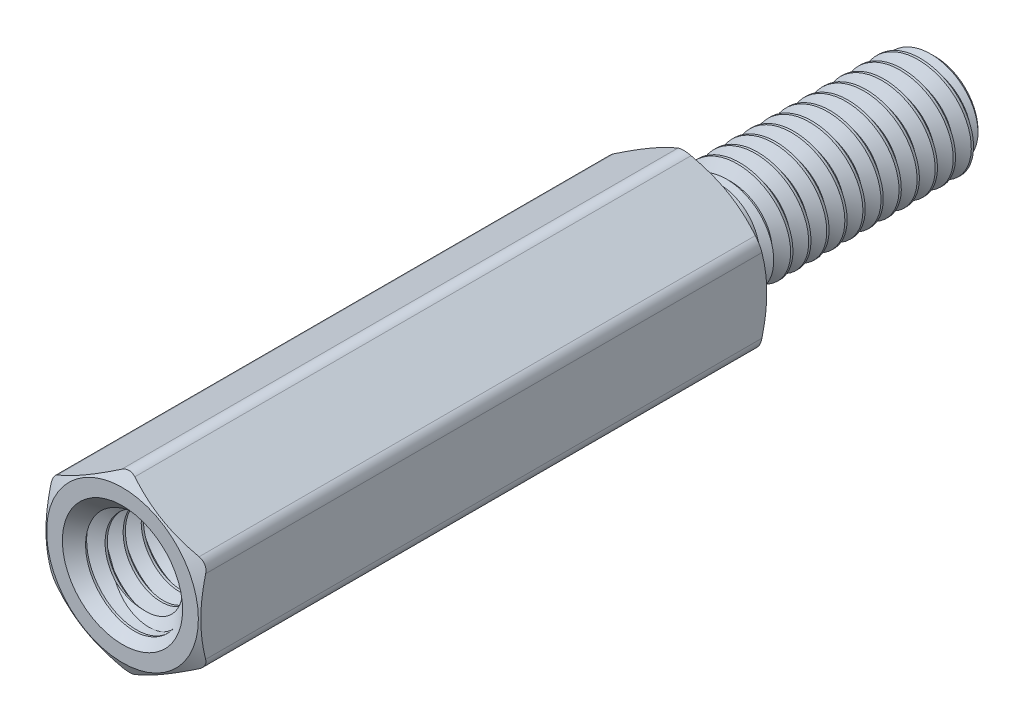
SolidWorks part; units mm, degrees
ref_plane "Front Plane" through (0, 0, 0) normal (0, 0, 1) x (1, 0, 0)
ref_plane "Top Plane" through (0, 0, 0) normal (0, 1, 0) x (1, 0, 0)
ref_plane "Right Plane" through (0, 0, 0) normal (1, 0, 0) x (0, 0, -1)
sketch "Sketch1" plane through (0, 0, 0) normal (0, 0, 1) x (1, 0, 0)
  line L1 (3, 1.7321) -> (0, 3.4641)
  line L2 (0, 3.4641) -> (-3, 1.7321)
  line L3 (-3, 1.7321) -> (-3, -1.7321)
  line L4 (-3, -1.7321) -> (0, -3.4641)
  line L5 (0, -3.4641) -> (3, -1.7321)
  line L6 (3, -1.7321) -> (3, 1.7321)
  circle A0 centre (0, 0) radius 3 construction
  point P10 (0, -3)
  dimension "Hex Size" = 6
sketch "Sketch2" plane through (0, 0, 0) normal (1, 0, 0) x (0, 0, -1)
  line L0 (9.5, 0) -> (-22, 0) construction
  line L2 (0, 2) -> (0, -2) construction
  line L3 (-10.9, 2) -> (-10.9, -2) construction
  line L4 (-22.6563, 2.0758) -> (-22.3063, 1.4696) construction
  line L5 (-22.3063, 1.4696) -> (-21.9563, 2.0758) construction
  line L6 (-21.9563, 2.0758) -> (-22.6563, 2.0758) construction
  line L7 (-22.6125, 2) -> (-22, 2) construction
  line L8 (-22.35, 1.5453) -> (-22.2625, 1.5453) construction
  line L9 (-22.3063, 1.5453) -> (-22.3063, 1.4696) construction
  line L10 (-22.3063, 2) -> (-22.3063, 2.0758) construction
  line L11 (9.4562, 2.0758) -> (10.1562, 2.0758) construction
  line L12 (10.1562, 2.0758) -> (9.8062, 1.4696) construction
  line L13 (9.8062, 1.4696) -> (9.4562, 2.0758) construction
  line L14 (9.5, 2) -> (10.1125, 2) construction
  line L15 (9.7625, 1.5453) -> (9.85, 1.5453) construction
  line L16 (9.8062, 1.5453) -> (9.8062, 1.4696) construction
  line L17 (9.8062, 2) -> (9.8062, 2.0758) construction
  line L18 (0, 3.4641) -> (-22, 3.4641) construction
  point P6 (0, 0)
  point P9 (-10.9, 0)
  dimension "Length" = 22
sketch "Sketch3" plane through (0, 0, 0) normal (1, 0, 0) x (0, 0, -1)
  line L0 (-10.9, 0) -> (9.5, 0)
  line L1 (-10.9, 2) -> (-10.9, -2) construction
  line L2 (9.5, 0) -> (9.5, 1.65)
  line L3 (9.5, 1.65) -> (9.15, 2)
  line L4 (9.15, 2) -> (1.4025, 2)
  line L5 (1.4025, 2) -> (1.14, 1.5453)
  line L6 (-10.9, 0) -> (-10.9, 1.65)
  line L7 (-10.9, 1.65) -> (-11.25, 2)
  line L8 (-11.25, 2) -> (-21.65, 2)
  line L9 (-21.65, 2) -> (-22, 2.35)
  line L10 (9.15, 0) -> (9.15, -2) construction
  line L11 (-22, 2.35) -> (-22, 3)
  line L12 (-22, 3) -> (0, 3)
  line L14 (1.14, 1.5453) -> (0.35, 1.5453)
  line L15 (0, 1.8953) -> (0, 3)
  arc A0 (0, 1.8953) -> (0.35, 1.5453) centre (0.35, 1.8953) ccw
  point P5 (-22, -3)
  point P8 (-20.25, -2)
  point P9 (7.75, -2)
  point P27 (0, 1.5453)
  dimension "D4" = 0.35
  dimension "D2" = 0.35
  dimension "D1" = 45
  dimension "D6" = 1.75
  dimension "D7" = 60
  dimension "D3" = 1.75
  dimension "D5" = 1.14
revolve "Revolve1" add sketch "Sketch3" angle 360 about L0
sketch "Sketch4" plane through (0, 0, 22) normal (0, 0, 1) x (1, 0, 0)
  line L0 (0, 3) -> (0, 2) construction
  line L1 (-3, 1.7321) -> (-3, -1.7321)
  line L2 (-3, -1.7321) -> (0, -3.4641)
  line L3 (0, -3.4641) -> (3, -1.7321)
  line L4 (3, -1.7321) -> (3, 1.7321)
  line L5 (3, 1.7321) -> (0, 3.4641)
  line L6 (0, 3.4641) -> (-3, 1.7321)
  circle A0 centre (0, 0) radius 3 construction
  circle A1 centre (0, 0) radius 2.5
  circle A2 centre (0, 0) radius 3 construction
  point P16 (0, 2.5)
extrude "Boss-Extrude1" add sketch "Sketch4" against normal up to surface (22 mm away) up to face at (0, 3, 0)
sketch "Sketch5" plane through (0, 0, 22) normal (0, 0, 1) x (1, 0, 0)
  line L0 (-1.1472, 1.6383) -> (1.1472, -1.6383) construction
  line L1 (0, 2) -> (0, -2) construction
  line L3 (0, -2.7928) -> (0, 2.7928) construction
  circle A0 centre (0, 0) radius 2.94
  point P11 (1.1472, -1.6383)
  dimension "D1" = 5.88
  dimension "D2" = 35
extrude "Cut-Extrude1" cut sketch "Sketch5" against normal through all draft 60 flip side to cut
sketch "Sketch6" plane through (0, 0, 0) normal (0, 0, -1) x (-1, 0, 0)
  circle A0 centre (0, 0) radius 2.94
  circle A1 centre (0, 0) radius 2.94 construction
extrude "Cut-Extrude2" cut sketch "Sketch6" against normal through all draft 60 flip side to cut
fillet "Fillet1" radius 0.51 6 edges at (0, 3.4641, 11) (-3, -1.7321, 11) (0, -3.4641, 11) (3, -1.7321, 11) (3, 1.7321, 11) (-3, 1.7321, 11)
sketch "Drawing1" plane through (0, 0, 0) normal (1, 0, 0) x (0, 0, -1)
  line L0 (-22, 2) -> (-10.9, 2) construction
  line L1 (-10.9, 2) -> (-10.9, -2) construction
  line L2 (-10.9, -2) -> (-22, -2) construction
sketch "Sketch7" plane through (0, 0, 0) normal (-1, 0, 0) x (0, 0, 1)
  line L0 (-9.7625, 1.5453) -> (-9.85, 1.5453)
  line L1 (-9.85, 1.5453) -> (-10.1344, 2.0379)
  line L2 (-10.1562, 2.0758) -> (-9.8062, 1.4696) construction
  line L3 (-10.1344, 2.0379) -> (-9.4781, 2.0379)
  line L4 (-9.8062, 1.4696) -> (-9.4562, 2.0758) construction
  line L5 (-9.4781, 2.0379) -> (-9.7625, 1.5453)
  line L6 (-9.8062, 2) -> (-9.8062, 2.0758) construction
  point P12 (-9.8062, 2.0379)
sketch "Sketch8" plane through (0, 0, -9.5) normal (0, 0, -1) x (-1, 0, 0)
  circle A0 centre (0, 0) radius 2
curve "Helix/Spiral1" pitch 0.7 height 9.215 turns 13.1643
sweep "Cut-Sweep1" cut profiles "Sketch7" path "Helix/Spiral1"
sketch "Sketch9" plane through (0, 0, 10.9) normal (0, 0, 1) x (1, 0, 0)
  circle A0 centre (0, 0) radius 2.35
extrude "Boss-Extrude2" add sketch "Sketch9" along normal up to surface (11.1 mm away)
sketch "Sketch10" plane through (0, 0, 0) normal (1, 0, 0) x (0, 0, -1)
  line L0 (9.5, 0) -> (-22, 0) construction
  line L1 (-10.9, 2) -> (-22, 2)
  line L2 (-10.9, 2) -> (-10.9, 0)
  line L3 (-10.9, 0) -> (-22, 0)
  line L4 (-22, 2) -> (-22, 0)
revolve "Revolve2" add sketch "Sketch10" angle 360 about L0
sketch "Sketch11" plane through (0, 0, 22) normal (0, 0, 1) x (1, 0, 0)
  circle A0 centre (0, 0) radius 2
  circle A1 centre (0, 0) radius 2 construction
sketch "Sketch12" plane through (0, 0, 0) normal (1, 0, 0) x (0, 0, -1)
  line L0 (-22.35, 1.5453) -> (-22.2625, 1.5453)
  line L1 (-22.2625, 1.5453) -> (-21.9781, 2.0379)
  line L2 (-22.3063, 1.4696) -> (-21.9563, 2.0758) construction
  line L3 (-21.9781, 2.0379) -> (-22.6344, 2.0379)
  line L4 (-22.6563, 2.0758) -> (-22.3063, 1.4696) construction
  line L5 (-22.6344, 2.0379) -> (-22.35, 1.5453)
  line L6 (-22.3063, 2) -> (-22.3063, 2.0758) construction
  point P12 (-22.3063, 2.0379)
curve "Helix/Spiral2" pitch 0.7 height 11.8 turns 16.8571
sweep "Cut-Sweep2" cut profiles "Sketch12" path "Helix/Spiral2"
combine bodies "Combine1" operation type subtract main body 113 bodies to subtract 114
sketch "Sketch13" plane through (0, 0, 22) normal (0, 0, 1) x (1, 0, 0)
  circle A0 centre (0, 0) radius 2.33
  dimension "D1" = 4.66
extrude "Cut-Extrude3" cut sketch "Sketch13" against normal through all draft 45
equation "\"Thread Pitch (B)/8@Sketch2\" = \"Thread Pitch (B)@Sketch2\" / 8"
equation "\"Thread Pitch (A)/8@Sketch2\" = \"Thread Pitch (A)@Sketch2\" / 8"
equation "\"D1@Sketch5\"=\"Hex Size@Sketch1\" * .98"
equation "\"D1@Fillet1\"=\"Hex Size@Sketch1\" * .085"
equation "\"D2@Sketch3\"=\"Thread Pitch (A)@Sketch2\" * .5"
equation "\"D4@Sketch3\" = \"D2@Sketch3\""
equation "\"D6@Sketch3\" = \"Thread Pitch (A)@Sketch2\" * 2.5"
equation "\"D3@Helix/Spiral1\" = \"Thread Length (A)@Sketch2\" - \"D5@Sketch3\" * .25"
equation "\"D4@Helix/Spiral1\" = \"Thread Pitch (A)@Sketch2\""
equation "\"D3@Sketch3\" = \"Thread Pitch (B)@Sketch2\" * 2.5"
equation "\"D5@Sketch3\" = \"Thread Length (A)@Sketch2\" * .12"
equation "\"D3@Helix/Spiral2\" = \"Minimum Thread Length (B)@Sketch2\" + \"Thread Pitch (B)@Sketch2\""
equation "\"D4@Helix/Spiral2\" = \"Thread Pitch (B)@Sketch2\""
equation "\"D1@Sketch13\"=(\"Hex Size@Sketch1\"-\"Thread Size (A)@Sketch2\")*.33+\"Thread Size (A)@Sketch2\""
